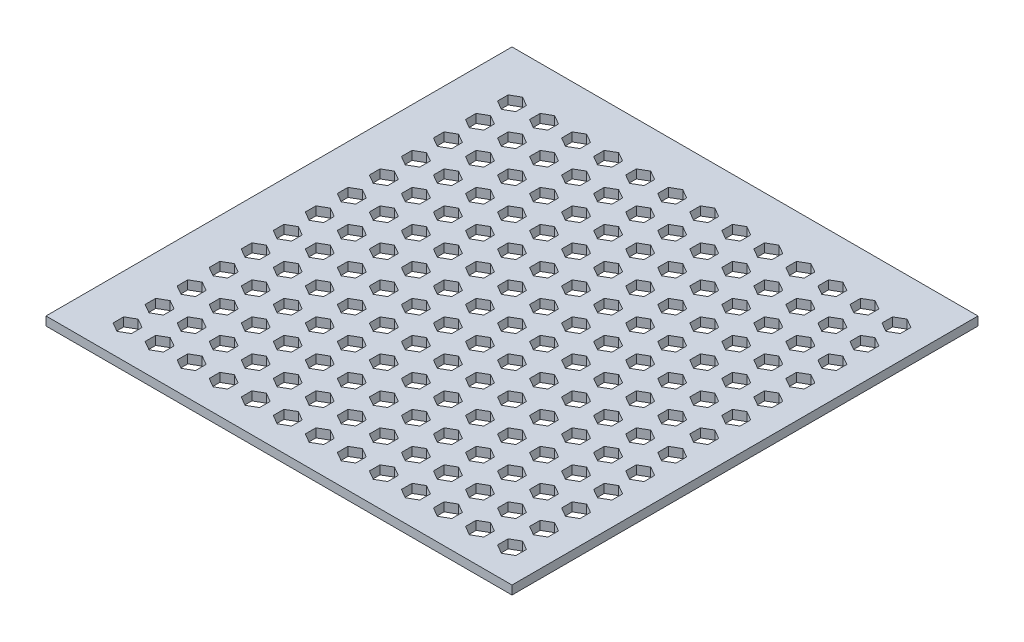
SolidWorks part; units mm, degrees
ref_plane "Front Plane" through (0, 0, 0) normal (0, 0, 1) x (1, 0, 0)
ref_plane "Top Plane" through (0, 0, 0) normal (0, 1, 0) x (1, 0, 0)
ref_plane "Right Plane" through (0, 0, 0) normal (1, 0, 0) x (0, 0, -1)
sketch "Sketch1" plane through (0, 0, 0) normal (0, 1, 0) x (1, 0, 0)
  line L1 (-80, -80) -> (80, -80)
  line L2 (-80, -80) -> (-80, 80)
  line L3 (-80, 80) -> (80, 80)
  line L4 (80, -80) -> (80, 80)
  line L5 (-80, -80) -> (80, 80) construction
  line L6 (-80, 80) -> (80, -80) construction
  point P0 (0, 0)
  dimension "D1" = 160
extrude "Boss-Extrude1" add sketch "Sketch1" along normal blind 3
sketch "Sketch2" plane through (0, 3, 0) normal (0, 1, 0) x (1, 0, 0)
  line L1 (2.75, 0.8873) -> (-0.4, -0.9313)
  line L2 (-0.4, -0.9313) -> (-0.4, -4.5687)
  line L3 (-0.4, -4.5687) -> (2.75, -6.3873)
  line L4 (2.75, -6.3873) -> (5.9, -4.5687)
  line L5 (5.9, -4.5687) -> (5.9, -0.9313)
  line L6 (5.9, -0.9313) -> (2.75, 0.8873)
  circle A0 centre (2.75, -2.75) radius 3.15 construction
  point P12 (0.5548, -2.1447)
  dimension "D1" = 6.3
  dimension "D2" = 2.75
  dimension "D3" = 2.75
extrude "Cut-Extrude1" cut sketch "Sketch2" against normal through all
pattern_linear "LPattern1" count 7 spacing 11 along (0, 0, 1) count 7 spacing 11 along (0, 0, -1) of "Cut-Extrude1"
pattern_linear "LPattern2" count 7 spacing 11 along (1, 0, 0) count 7 spacing 11 along (-1, 0, 0) of "LPattern1", "Cut-Extrude1"
